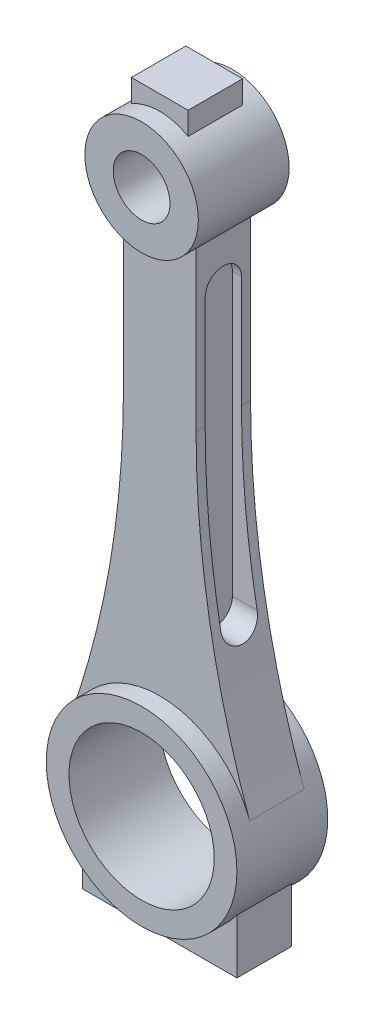
SolidWorks part; units mm, degrees
ref_plane "Front Plane" through (0, 0, 0) normal (0, 0, 1) x (1, 0, 0)
ref_plane "Top Plane" through (0, 0, 0) normal (0, 1, 0) x (1, 0, 0)
ref_plane "Right Plane" through (0, 0, 0) normal (1, 0, 0) x (0, 0, -1)
sketch "Sketch2" plane through (0, 0, 0) normal (0, 0, 1) x (1, 0, 0)
  line L0 (0, -3.8664) -> (0, -37.8664) construction
  line L1 (-8, 110.3953) -> (-8, 75.3953)
  line L2 (8, 110.3953) -> (8, 75.3953)
  line L3 (-6.25, 130.8253) -> (-6.25, 135.8253)
  line L4 (-6.25, 135.8253) -> (6.25, 135.8253)
  line L5 (6.25, 135.8253) -> (6.25, 130.8253)
  line L6 (-17, -24.3288) -> (17, -24.3288)
  line L7 (17, -24.3288) -> (17, -12.3288)
  line L8 (-17, -24.3288) -> (-17, -12.3288)
  circle A0 centre (0, 0) radius 21
  circle A1 centre (0, 0) radius 16
  circle A2 centre (0, 120) radius 12.5
  circle A3 centre (0, 120) radius 6.25
  arc A4 (-8, 75.3953) -> (-19.7874, 7.0327) centre (-212.1328, 75.3953) cw
  arc A5 (8, 75.3953) -> (19.7874, 7.0327) centre (212.1328, 75.3953) ccw
  dimension "D1" = 42
  dimension "D2" = 32
  dimension "D3" = 25
  dimension "D4" = 12.5
  dimension "D5" = 120
  dimension "D6" = 35
  dimension "D7" = 8
  dimension "D8" = 12.5
  dimension "D9" = 5
  dimension "D10" = 34
  dimension "D11" = 12
extrude "Boss-Extrude1" add sketch "Sketch2" along normal mid plane 20 contours A2 A3 | A1 A0 region at (-12.1021, 121.0366, 0) region at (0, 20.406, 0)
extrude "Boss-Extrude2" add sketch "Sketch2<4>" along normal mid plane 12 contours A5 L2 A2 L1 A4 A0 | A2 L5 L4 L3 | L0 A0 L8 L6 | A0 L0 L6 L7 region at (10.4494, -20.8498, 0) region at (-10.4494, -20.8498, 0) region at (0, 57.8448, 0) region at (0, 133.8599, 0)
sketch "Sketch2<4>" plane through (0, 0, 0) normal (0, 0, 1) x (1, 0, 0) same geometry as "Sketch2"
sketch "Sketch3" plane through (0, 0, 0) normal (1, 0, 0) x (0, 0, -1)
  line L0 (0, 100) -> (0, 38) construction
  line L3 (4, 100) -> (4, 38)
  line L4 (-4, 100) -> (-4, 38)
  arc A2 (4, 100) -> (-4, 100) centre (0, 100) ccw
  arc A3 (-4, 38) -> (4, 38) centre (0, 38) ccw
  point P3 (0, 69)
  point P8 (0, 0)
  dimension "D2" = 62
  dimension "D3" = 4
  dimension "D1" = 100
extrude "Cut-Extrude1" cut sketch "Sketch3" along normal through all from offset 6
extrude "Cut-Extrude2" cut sketch "Sketch3<2>" against normal through all from offset 6 offset against normal yes
sketch "Sketch3<2>" plane through (0, 0, 0) normal (1, 0, 0) x (0, 0, -1) same geometry as "Sketch3"
